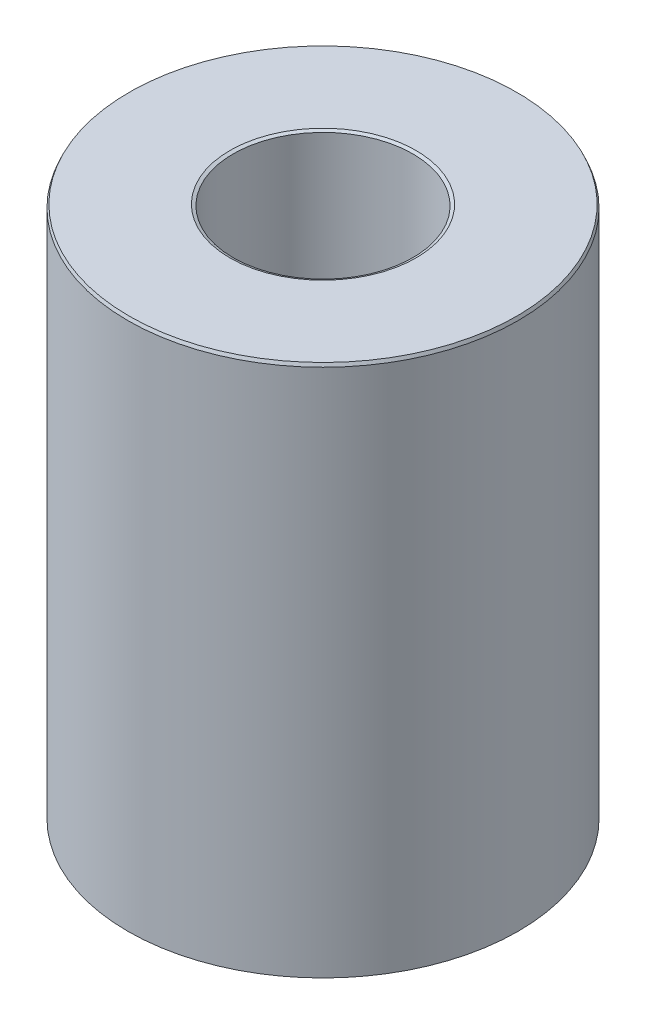
SolidWorks part; units mm, degrees
ref_plane "Front Plane" through (0, 0, 0) normal (0, 0, 1) x (1, 0, 0)
ref_plane "Top Plane" through (0, 0, 0) normal (0, 1, 0) x (1, 0, 0)
ref_plane "Right Plane" through (0, 0, 0) normal (1, 0, 0) x (0, 0, -1)
sketch "Sketch1" plane through (0, 0, 0) normal (0, 1, 0) x (1, 0, 0)
  circle A0 centre (0, 0) radius 40
  dimension "SLEEVE_OD" = 80
extrude "Boss-Extrude1" add sketch "Sketch1" along normal blind 109.3138
sketch "Sketch2" plane through (0, 0, 0) normal (0, 1, 0) x (1, 0, 0)
  circle A0 centre (0, 0) radius 18.4221
  dimension "BORE_D" = 36.8441
extrude "Cut-Extrude1" cut sketch "Sketch2" along normal through all
chamfer "Chamfer1" distance 0.6535 angle 22.968 4 edges at (0, 109.3138, 18.4221) (0, 0, 18.4221) (0, 0, 40) (0, 109.3138, 40) first distance on face at (0, 109.3138, 18.4221) first distance on face at (0, 0, 18.4221) first distance on face at (0, 109.3138, 40)
